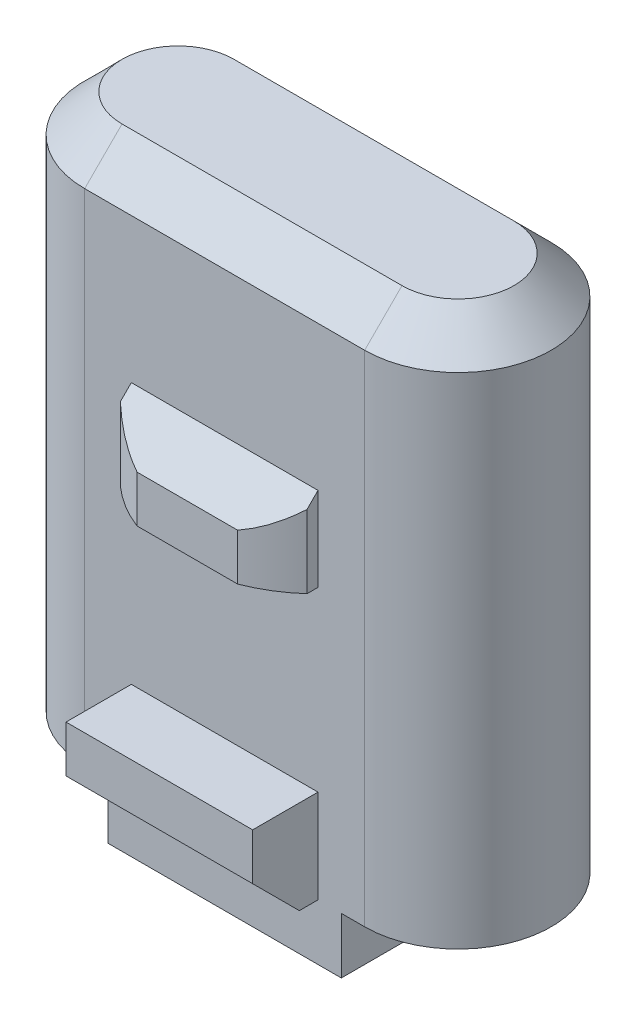
SolidWorks part; units mm, degrees
ref_plane "前视基准面" through (0, 0, 0) normal (0, 0, 1) x (1, 0, 0)
ref_plane "上视基准面" through (0, 0, 0) normal (0, 1, 0) x (1, 0, 0)
ref_plane "右视基准面" through (0, 0, 0) normal (1, 0, 0) x (0, 0, -1)
other "Configuration Table"
sketch "草图2" plane through (0, 0, 0) normal (0, 1, 0) x (1, 0, 0)
  line L0 (0, 0) -> (6, 0) construction
  line L1 (0, 2) -> (6, 2)
  line L2 (0, -2) -> (6, -2)
  arc A0 (0, 2) -> (0, -2) centre (0, 0) ccw
  arc A1 (6, -2) -> (6, 2) centre (6, 0) ccw
  point P3 (3, 0)
  dimension "D2" = 2
  dimension "D1" = 6
extrude "凸台-拉伸1" add sketch "草图2" along normal blind 12.7
sketch "草图3" plane through (0, 0, 2) normal (0, 0, 1) x (1, 0, 0)
  line L0 (-2, 0) -> (0, 0) construction
  line L1 (-2, 0) -> (0.5, 0)
  line L2 (-2, 0) -> (-2, 1.2)
  line L3 (-2, 1.2) -> (0.5, 1.2)
  line L4 (0.5, 0) -> (0.5, 1.2)
  line L5 (-2, 0) -> (0.5, 1.2) construction
  line L6 (-2, 1.2) -> (0.5, 0) construction
  line L7 (3, 12.7) -> (3, 0) construction
  line L8 (8, 0) -> (5.5, 0)
  line L9 (8, 0) -> (8, 1.2)
  line L10 (8, 1.2) -> (5.5, 1.2)
  line L11 (5.5, 0) -> (5.5, 1.2)
  line L12 (8, 0) -> (5.5, 1.2) construction
  line L13 (8, 1.2) -> (5.5, 0) construction
  line L14 (0, 12.7) -> (6, 12.7) construction
  line L15 (0, 0) -> (6, 0) construction
  line L16 (-2, 12.7) -> (-2, 0) construction
  point P4 (-0.75, 0.6)
  point P11 (6.75, 0.6)
  dimension "D1" = 1.2
  dimension "D2" = 2.5
extrude "切除-拉伸1" cut sketch "草图3" against normal up to next
ref_plane "基准面1" through (3, 0, 0) normal (-1, 0, 0) x (0, 0, 1)
sketch "草图5" plane through (3, 0, 0) normal (-1, 0, 0) x (0, 0, 1)
  line L0 (-2, 7) -> (-2.8, 7)
  line L1 (-2, 12.7) -> (-2, 1.2) construction
  line L2 (-2.8, 7) -> (-2.8, 8)
  line L3 (-2.8, 8) -> (-2, 8.8)
  line L4 (-2, 8.8) -> (-2, 7)
  line L5 (-2, 0) -> (2, 0) construction
  line L6 (0, 1.2) -> (0, 12.7) construction
  line L7 (-2, 1.2) -> (2, 1.2) construction
  line L8 (2, 12.7) -> (-2, 12.7) construction
  line L9 (2, 8.8) -> (2, 7)
  line L10 (2.8, 8) -> (2, 8.8)
  line L11 (2.8, 7) -> (2.8, 8)
  line L12 (2, 7) -> (2.8, 7)
  line L14 (-2, 1.2) -> (-3.4, 1.2)
  line L15 (-2, 1.2) -> (-2, 3.2)
  line L16 (-2, 3.2) -> (-3.4, 3.2)
  line L17 (-3.4, 1.2) -> (-3.4, 3.2)
  line L18 (-2, 1.2) -> (-3.4, 3.2) construction
  line L19 (-2, 3.2) -> (-3.4, 1.2) construction
  line L24 (2, 3.2) -> (3.4, 1.2) construction
  line L25 (2, 1.2) -> (3.4, 3.2) construction
  line L26 (3.4, 1.2) -> (3.4, 3.2)
  line L27 (2, 3.2) -> (3.4, 3.2)
  line L28 (2, 1.2) -> (2, 3.2)
  line L29 (2, 1.2) -> (3.4, 1.2)
  point P22 (-2.7, 2.2)
  point P27 (2.7, 2.2)
  dimension "D1" = 7
  dimension "D2" = 0.8
  dimension "D3" = 1
  dimension "D4" = 45
  dimension "D5" = 1.4
  dimension "D6" = 3.2
  dimension "D7" = 2
extrude "凸台-拉伸2" add sketch "草图5" along normal blind 2 and the other way blind 2
sketch "草图6" plane through (0, 12.7, 0) normal (0, 1, 0) x (1, 0, 0)
  line L0 (3, 0.66) -> (3, -0.66) construction
  line L1 (1.923, 2.8) -> (1, 2.8)
  line L2 (4.077, -2.8) -> (5, -2.8)
  line L5 (5, 2.8) -> (1, 2.8)
  line L6 (1, 2.8) -> (1, 2)
  line L7 (1, 2) -> (5, 2)
  line L8 (5, 2) -> (5, 2.8)
  line L9 (5, 2.8) -> (4.077, 2.8)
  line L10 (1, 2.8) -> (1, 2.2361)
  line L12 (5, 2.2361) -> (5, 2.8)
  line L13 (5, -2) -> (1, -2)
  line L14 (1, -2) -> (1, -2.8)
  line L15 (1, -2.8) -> (5, -2.8)
  line L16 (5, -2.8) -> (5, -2)
  line L18 (1, -2.2361) -> (1, -2.8)
  line L19 (1, -2.8) -> (1.923, -2.8)
  line L20 (5, -2.8) -> (5, -2.2361)
  arc A0 (1, -2.2361) -> (1.923, -2.8) centre (3, 0) ccw
  arc A1 (5, 2.2361) -> (4.077, 2.8) centre (3, 0) ccw
  arc A2 (1.923, 2.8) -> (1, 2.2361) centre (3, 0) ccw
  arc A3 (4.077, -2.8) -> (5, -2.2361) centre (3, 0) ccw
  point P4 (3, 0)
  dimension "D1" = 6
  dimension "D2" = 0
  dimension "D3" = 0
extrude "切除-拉伸2" cut sketch "草图6" against normal up to next
chamfer "倒角1" distance 1 angle 45 2 edges at (3, 1.2, 3.4) (3, 1.2, -3.4)
chamfer "倒角2" distance 0.8 angle 45 4 edges at (8, 12.7, 0) (3, 12.7, -2) (3, 12.7, 2) (-2, 12.7, 0)
